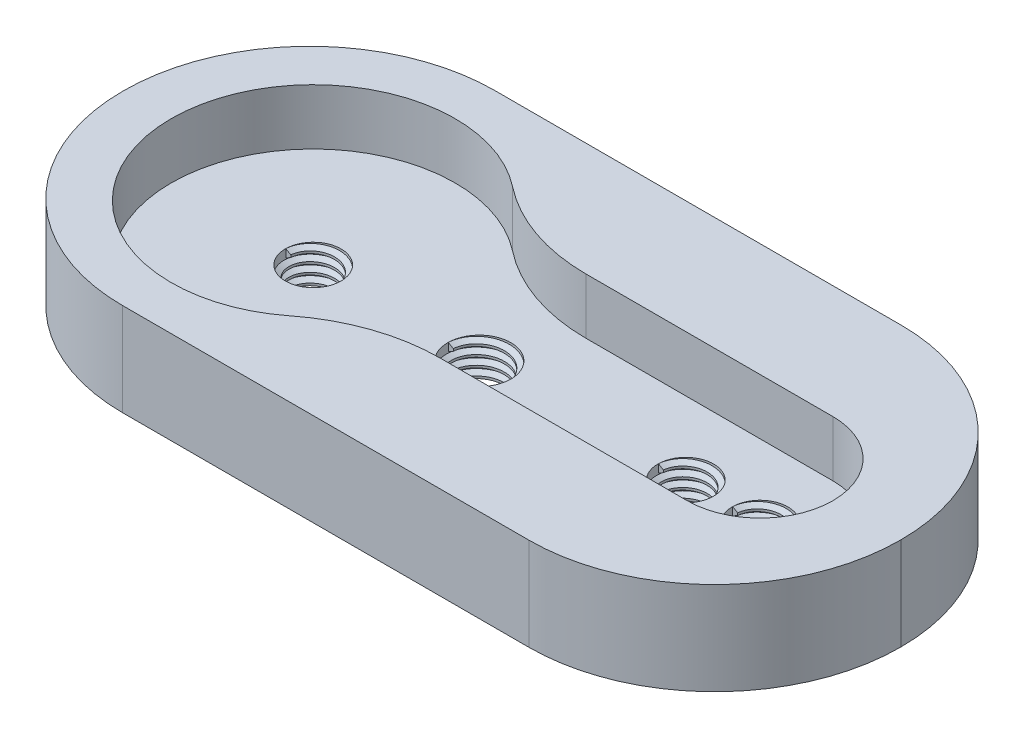
SolidWorks part; units mm, degrees
other "Markup1"
sketch "Sketch4" plane through (-10.2334, 0, -10.0285) normal (0, 1, 0) x (1, 0, 0)
other "DetailItem1"
other "Markup2"
sketch "Sketch5" plane through (-10.2334, 0, -10.0285) normal (0, 1, 0) x (1, 0, 0)
ref_plane "Front Plane" through (0, 0, 0) normal (0, 0, 1) x (1, 0, 0)
ref_plane "Top Plane" through (0, 0, 0) normal (0, 1, 0) x (1, 0, 0)
ref_plane "Right Plane" through (0, 0, 0) normal (1, 0, 0) x (0, 0, -1)
sketch "Sketch2" plane through (0, 0, 0) normal (0, 1, 0) x (1, 0, 0)
  line L0 (24.0717, 0) -> (20.0717, 0) construction
  line L1 (10.7762, 3.725) -> (24.0717, 3.725)
  line L2 (24.0717, -3) -> (20.0717, -3)
  line L3 (10.7762, -3.725) -> (24.0717, -3.725)
  line L4 (24.0717, 3) -> (20.0717, 3)
  line L5 (10.7762, -3.925) -> (24.0717, -3.925)
  line L6 (10.7762, 3.925) -> (24.0717, 3.925)
  arc A1 (24.0717, -3.725) -> (24.0717, 3.725) centre (24.0717, 0) ccw
  arc A2 (24.0717, -3) -> (24.0717, 3) centre (24.0717, 0) ccw
  arc A4 (6.4519, 3.725) -> (7.4142, 0.729) centre (0, 0) cw
  arc A9 (4.6007, -5.8597) -> (10.7762, -3.725) centre (10.7762, -13.725) cw
  arc A10 (4.6007, 5.8597) -> (10.7762, 3.725) centre (10.7762, 13.725) ccw
  arc A11 (4.7242, 6.017) -> (4.7242, -6.017) centre (0, 0) ccw
  arc A12 (4.7242, -6.017) -> (10.7762, -3.925) centre (10.7762, -13.725) cw
  arc A13 (24.0717, -3.925) -> (24.0717, 3.925) centre (24.0717, 0) ccw
  arc A14 (4.7242, 6.017) -> (10.7762, 3.925) centre (10.7762, 13.725) ccw
  arc A15 (4.6007, 5.8597) -> (4.6007, -5.8597) centre (0, 0) ccw construction
  circle A16 centre (0, 0) radius 1.5
  circle A17 centre (8.95, 0) radius 1.7
  circle A18 centre (20.0717, 0) radius 1.5
  circle A19 centre (24.0717, 0) radius 1.5
  arc A20 (7.4142, -0.729) -> (6.4519, -3.725) centre (0, 0) cw
  point P1 (22.0717, 0)
  dimension "D2" = 7.45
  dimension "D6" = 3
  dimension "D7" = 3
  dimension "D10" = 10
  dimension "D5" = 3
  dimension "D3" = 24.0717
  dimension "D4" = 6
  dimension "D11" = 0.2
sketch "Sketch3" plane through (0, 0, 0) normal (0, 1, 0) x (1, 0, 0)
  line L1 (-10.2334, 10.0285) -> (31.653, 10.0285)
  line L2 (-10.2334, 10.0285) -> (-10.2334, -10.0285)
  line L3 (-10.2334, -10.0285) -> (31.653, -10.0285)
  line L4 (31.653, 10.0285) -> (31.653, -10.0285)
extrude "Boss-Extrude" add sketch "Sketch3" against normal blind 5
fillet "Fillet1" radius 10 4 edges at (-10.2334, -2.5, -10.0285) (31.653, -2.5, -10.0285) (31.653, -2.5, 10.0285) (-10.2334, -2.5, 10.0285)
extrude "Cut-Extrude1" cut sketch "Sketch2" against normal blind 3 contours A14 A11 A12 L5 A13 L6 L4 A2 L2 | L4 L2 A2 region at (7.4478, 0, 4.0961)
extrude "Cut-Extrude2" cut sketch "Sketch2<4>" against normal blind 7 contours A17 | A18 | A19 | A16 region at (8.95, 0, 0) region at (20.0717, 0, 0) region at (24.0717, 0, 0)
sketch "Sketch2<4>" plane through (0, 0, 0) normal (0, 1, 0) x (1, 0, 0) same geometry as "Sketch2"
thread "Thread1" pitch 0.5 method extrude profile "Thread Profile1" start angle 1, offset 0, length 0, pitch 0.5, diameter 3
ref_plane "Plane1" through (-1.4998, -3, -0.0262) normal (-0.0175, 0, 0.9998) x (-0.9998, 0, -0.0175)
sketch "Thread Profile1" plane through (-1.4998, -3, -0.0262) normal (-0.0175, 0, 0.9998) x (-0.9998, 0, -0.0175)
  line L0 (0, 0) -> (0, 0.5) construction
  line L11 (0, 0) -> (0, 0.4375)
  line L12 (0, 0.4375) -> (-0.2706, 0.2812)
  line L13 (-0.2706, 0.2812) -> (-0.2706, 0.1562)
  line L15 (-0.2706, 0.1562) -> (0, 0)
  line L17 (-0.2706, 0.2187) -> (0, 0.2187) construction
  point P2 (0, 0)
  dimension "Pitch" = 0.5
  dimension "Profile_Angle" = 60
  dimension "Profile_Land" = 0.125
  dimension "Profile_Height" = 0.2706
thread "Thread2" pitch 0.5 method extrude profile "Thread Profile2" start angle 1, offset 0, length 0, pitch 0.5, diameter 3
ref_plane "Plane2" through (18.5719, -3, -0.0262) normal (-0.0175, 0, 0.9998) x (-0.9998, 0, -0.0175)
sketch "Thread Profile2" plane through (18.5719, -3, -0.0262) normal (-0.0175, 0, 0.9998) x (-0.9998, 0, -0.0175)
  line L0 (0, 0) -> (0, 0.5) construction
  line L11 (0, 0) -> (0, 0.4375)
  line L12 (0, 0.4375) -> (-0.2706, 0.2812)
  line L13 (-0.2706, 0.2812) -> (-0.2706, 0.1562)
  line L15 (-0.2706, 0.1562) -> (0, 0)
  line L17 (-0.2706, 0.2187) -> (0, 0.2187) construction
  point P2 (0, 0)
  dimension "Pitch" = 0.5
  dimension "Profile_Angle" = 60
  dimension "Profile_Land" = 0.125
  dimension "Profile_Height" = 0.2706
thread "Thread3" pitch 0.5 method extrude profile "Thread Profile3" start angle 1, offset 0, length 0, pitch 0.5, diameter 3
ref_plane "Plane3" through (22.5719, -3, -0.0262) normal (-0.0175, 0, 0.9998) x (-0.9998, 0, -0.0175)
sketch "Thread Profile3" plane through (22.5719, -3, -0.0262) normal (-0.0175, 0, 0.9998) x (-0.9998, 0, -0.0175)
  line L0 (0, 0) -> (0, 0.5) construction
  line L11 (0, 0) -> (0, 0.4375)
  line L12 (0, 0.4375) -> (-0.2706, 0.2812)
  line L13 (-0.2706, 0.2812) -> (-0.2706, 0.1562)
  line L15 (-0.2706, 0.1562) -> (0, 0)
  line L17 (-0.2706, 0.2187) -> (0, 0.2187) construction
  point P2 (0, 0)
  dimension "Pitch" = 0.5
  dimension "Profile_Angle" = 60
  dimension "Profile_Land" = 0.125
  dimension "Profile_Height" = 0.2706
thread "Thread4" pitch 0.5 method extrude profile "Thread Profile4" start angle 1, offset 0, length 0, pitch 0.5, diameter 3.4
ref_plane "Plane4" through (7.2503, -3, -0.0297) normal (-0.0175, 0, 0.9998) x (-0.9998, 0, -0.0175)
sketch "Thread Profile4" plane through (7.2503, -3, -0.0297) normal (-0.0175, 0, 0.9998) x (-0.9998, 0, -0.0175)
  line L0 (0, 0) -> (0, 0.5) construction
  line L11 (0, 0) -> (0, 0.4375)
  line L12 (0, 0.4375) -> (-0.2706, 0.2812)
  line L13 (-0.2706, 0.2812) -> (-0.2706, 0.1562)
  line L15 (-0.2706, 0.1562) -> (0, 0)
  line L17 (-0.2706, 0.2187) -> (0, 0.2187) construction
  point P2 (0, 0)
  dimension "Pitch" = 0.5
  dimension "Profile_Angle" = 60
  dimension "Profile_Land" = 0.125
  dimension "Profile_Height" = 0.2706
